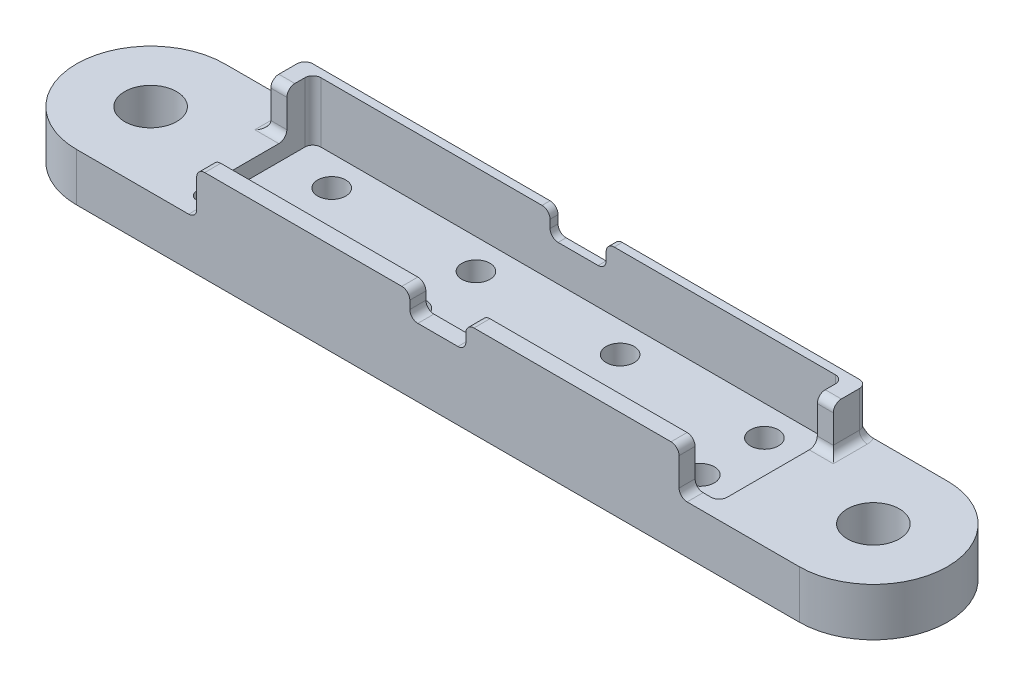
SolidWorks part; units mm, degrees
material "Delrin 2700 NC010, Low Viscosity Acetal Copolymer (SS)"
ref_plane "Front Plane" through (0, 0, 0) normal (0, 0, 1) x (1, 0, 0)
ref_plane "Top Plane" through (0, 0, 0) normal (0, 1, 0) x (1, 0, 0)
ref_plane "Right Plane" through (0, 0, 0) normal (1, 0, 0) x (0, 0, -1)
sketch "Sketch1" plane through (0, 0, 0) normal (0, 1, 0) x (1, 0, 0)
  line L1 (-35.1, -9.25) -> (0, -9.25)
  line L2 (-35.1, -9.25) -> (-35.1, 9.25)
  line L3 (-35.1, 9.25) -> (0, 9.25)
  line L4 (0, -9.25) -> (0, 9.25)
  line L5 (-35.1, -9.25) -> (0, 9.25) construction
  line L6 (-35.1, 9.25) -> (0, -9.25) construction
  point P0 (-17.55, 0)
  point P8 (0, 0)
  dimension "D1" = 35.1
  dimension "D2" = 18.5
extrude "Boss-Extrude1" add sketch "Sketch1" along normal blind 11.5
shell "Shell1" [suppressed] thickness 1
sketch "Sketch7" plane through (0, 11.5, 0) normal (0, 1, 0) x (1, 0, 0)
  line L0 (0, -9.25) -> (0, 9.25) construction
  line L1 (0, -7.25) -> (-33.1, -7.25)
  line L2 (0, -7.25) -> (0, 8.25)
  line L3 (0, 8.25) -> (-33.1, 8.25)
  line L4 (-33.1, -7.25) -> (-33.1, 8.25)
  line L5 (-35.1, -9.25) -> (0, -9.25) construction
  line L6 (0, 9.25) -> (-35.1, 9.25) construction
  line L7 (-35.1, 9.25) -> (-35.1, -9.25) construction
  dimension "D1" = 2
  dimension "D2" = 1
  dimension "D3" = 2
extrude "Cut-Extrude5" cut sketch "Sketch7" against normal offset from surface (7.5 mm away) 4 up to face at (-17.55, 0, 0)
sketch "Sketch2" plane through (0, 0, 0) normal (0, 1, 0) x (-1, 0, 0)
  line L0 (27, 3.5) -> (9, 3.5) construction
  line L2 (27, 3.5) -> (27, -4.5) construction
  line L3 (27, -4.5) -> (9, -4.5) construction
  line L4 (9, -4.5) -> (9, 3.5) construction
  line L5 (27, -0.5) -> (18.8977, -0.5) construction
  line L6 (17.55, -9.25) -> (17.55, 9.25) construction
  line L7 (0, 7.25) -> (0, -8.25) construction
  line L8 (27, -0.5) -> (0, -0.5) construction
  line L9 (0, -9.25) -> (35.1, -9.25) construction
  line L10 (35.1, 9.25) -> (0, 9.25) construction
  circle A0 centre (27, 3.5) radius 1.75
  circle A1 centre (9, 3.5) radius 1.75
  circle A2 centre (27, -4.5) radius 1.75
  circle A3 centre (9, -4.5) radius 1.75
  circle A5 centre (27, 3.5) radius 2.5 construction
  circle A6 centre (27, -4.5) radius 2.5 construction
  circle A7 centre (9, -4.5) radius 2.5 construction
  circle A8 centre (9, 3.5) radius 2.5 construction
  dimension "D1" = 3.5
  dimension "D4" = 9
  dimension "D5" = 5
  dimension "D2" = 18
  dimension "D3" = 8
extrude "Cut-Extrude1" cut sketch "Sketch2" along normal through all
sketch "Sketch3" [suppressed] plane through (0, 5, 0) normal (0, 1, 0) x (1, 0, 0)
  line L1 (-2.9573, -5.1559) -> (2.9865, -5.139)
  line L2 (2.9865, -5.139) -> (5.9438, 0.0169)
  line L3 (5.9438, 0.0169) -> (2.9573, 5.1559)
  line L4 (2.9573, 5.1559) -> (-2.9865, 5.139)
  line L5 (-2.9865, 5.139) -> (-5.9438, -0.0169)
  line L6 (-5.9438, -0.0169) -> (-2.9573, -5.1559)
  circle A0 centre (0, 0) radius 2.6 construction
  circle A1 centre (0, 0) radius 5.1475 construction
  dimension "D1" = 5.2
extrude "Cut-Extrude2" [suppressed] cut sketch "Sketch3" against normal blind 0.5
sketch "Sketch4" plane through (-35.1, 0, 0) normal (-1, 0, 0) x (0, 0, 1)
  line L0 (-9.25, 11.5) -> (9.25, 11.5) construction
  line L1 (-5, 11.5) -> (9.25, 11.5)
  line L3 (-5, 6) -> (9.25, 6)
  line L4 (9.25, 11.5) -> (9.25, 6)
  line L5 (0, 6) -> (0, 0) construction
  line L11 (-9.25, 0) -> (9.25, 0) construction
  line L12 (-5, 6) -> (-5, 11.5)
  dimension "D1" = 5
  dimension "D2" = 5.5
extrude "Cut-Extrude3" cut sketch "Sketch4" against normal offset from surface (5 mm away) 3 up to face at (-33.1, 7.75, -0.5) offset beyond the face yes
sketch "Sketch8" plane through (0, 0, 0) normal (0, -1, 0) x (-1, 0, 0)
  line L0 (35.1, -9.25) -> (45.1, -9.25)
  line L1 (35.1, 9.25) -> (45.1, 9.25)
  line L2 (35.1, 9.25) -> (35.1, -9.25)
  arc A0 (45.1, 9.25) -> (45.1, -9.25) centre (45.1, 0) cw
  circle A1 centre (45.1, 0) radius 3.25
  dimension "D2" = 6.5
  dimension "D1" = 10
extrude "bolt extrude" add sketch "Sketch8" against normal blind 6
mirror "Mirror1" about plane through (0, 0, 0) normal (1, 0, 0) of bodies 112 105
sketch "Sketch5" plane through (0, 0, 0) normal (0, 1, 0) x (1, 0, 0)
  line L0 (33.1, 0.5) -> (0, 0.5) construction
  line L1 (33.1, 8.25) -> (33.1, -7.25) construction
  line L4 (0, 0.5) -> (0, 0) construction
  circle A0 centre (0, 0.5) radius 2.75
  dimension "D1" = 5.5
extrude "Cut-Extrude4" [suppressed] cut sketch "Sketch5" along normal through all
sketch "Sketch6" [suppressed] plane through (0, 4, 0) normal (0, 1, 0) x (1, 0, 0)
  circle A0 centre (0, 0.5) radius 6.25
  circle A1 centre (0, 0.5) radius 5.25
  circle A2 centre (0, 0.5) radius 2.75 construction
  dimension "D1" = 10.5
  dimension "D2" = 1
extrude "Boss-Extrude2" [suppressed] add sketch "Sketch6" along normal blind 3.5
fillet "Fillet3" radius 1 8 edges at (30.1, 6, 8.25) (-30.1, 6, 8.25) (30.1, 11.5, 8.25) (-30.1, 11.5, 8.25) (34.1, 11.5, -5) (34.1, 6, -5) (-34.1, 11.5, -5) (-34.1, 6, -5)
fillet "Fillet4" [suppressed] radius 0.5
fillet "Fillet5" [suppressed] radius 0.5
sketch "Sketch9" plane through (0, 11.5, 0) normal (0, 1, 0) x (1, 0, 0)
  line L0 (35.1, 9.25) -> (-35.1, 9.25) construction
  line L1 (-3.5, 9.25) -> (3.5, 9.25)
  line L2 (-3.5, 9.25) -> (-3.5, -9.25)
  line L3 (-3.5, -9.25) -> (3.5, -9.25)
  line L4 (3.5, 9.25) -> (3.5, -9.25)
  line L5 (-29.1, -9.25) -> (29.1, -9.25) construction
  dimension "D1" = 3.5
  dimension "D2" = 3.5
extrude "Cut-Extrude6" cut sketch "Sketch9" against normal blind 3
fillet "Fillet6" radius 1 14 edges at (35.1, 8.75, -9.25) (-35.1, 8.75, -9.25) (-33.1, 5, 7.25) (-33.1, 7.75, -8.25) (33.1, 7.75, -8.25) (33.1, 5, 7.25) (-3.5, 8.5, -8.75) (3.5, 8.5, -8.75) (3.5, 8.5, 8.25) (-3.5, 8.5, 8.25) (3.5, 11.5, 8.25) (-3.5, 11.5, 8.25) (-3.5, 11.5, -8.75) (3.5, 11.5, -8.75)
fillet "Fillet7" [suppressed] radius 1
fillet "Fillet8" [suppressed] radius 1
fillet "Fillet9" radius 1 4 edges at (-35.1, 6, -6.125) (-34.8071, 6, -8.9571) (35.1, 6, -6.125) (34.8071, 6, -8.9571)
